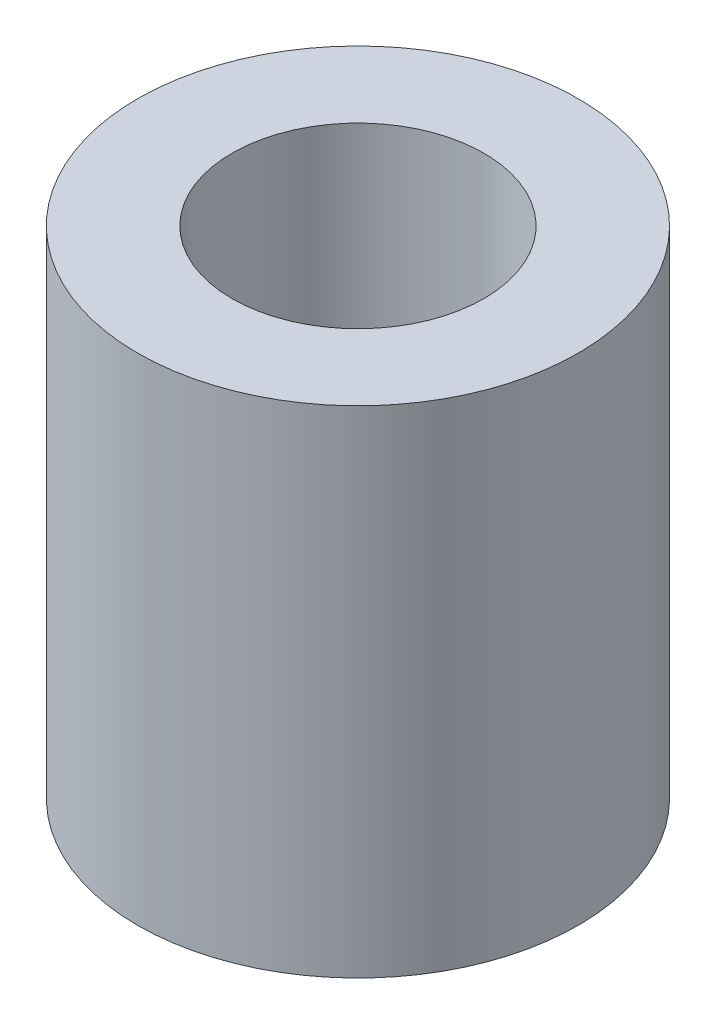
SolidWorks part; units mm, degrees
ref_plane "Front" through (0, 0, 0) normal (0, 0, 1) x (1, 0, 0)
ref_plane "Top" through (0, 0, 0) normal (0, 1, 0) x (1, 0, 0)
ref_plane "Right" through (0, 0, 0) normal (1, 0, 0) x (0, 0, -1)
sketch "Sketch2" plane through (0, 0, 0) normal (0, 1, 0) x (1, 0, 0)
  circle A0 centre (0, 0) radius 5.335
  circle A1 centre (0, 0) radius 3.05
  dimension "D1" = 10.67
  dimension "D2" = 6.1
extrude "Boss-Extrude1" add sketch "Sketch2" along normal blind 12
